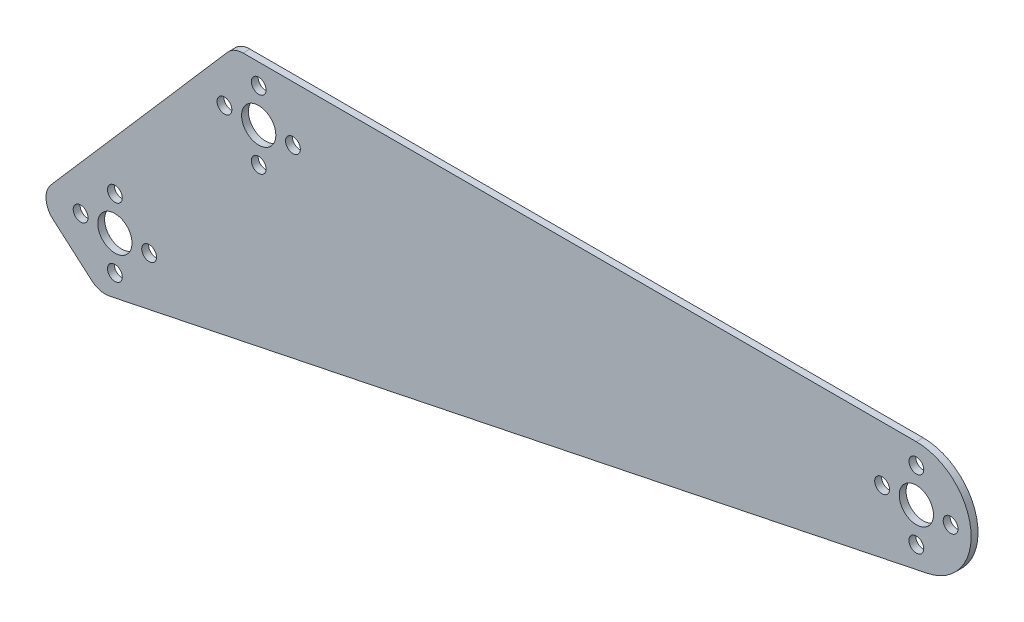
SolidWorks part; units mm, degrees
ref_plane "Front Plane" through (0, 0, 0) normal (0, 0, 1) x (1, 0, 0)
ref_plane "Top Plane" through (0, 0, 0) normal (0, 1, 0) x (1, 0, 0)
ref_plane "Right Plane" through (0, 0, 0) normal (1, 0, 0) x (0, 0, -1)
sketch "Sketch1" plane through (0, 0, 0) normal (0, 0, 1) x (1, 0, 0)
  line L0 (0, 0) -> (-66.6556, -76.6785) construction
  line L1 (55, 0) -> (-55, 0) construction
  line L2 (304.8, 25.4) -> (-7.2347, 25.4)
  line L3 (-96.2402, -71.9956) -> (-14.4233, 22.124)
  line L4 (-69.2153, -103.1424) -> (309.935, -24.8755)
  line L5 (0, 15.875) -> (0, -15.875) construction
  line L6 (-15.875, 0) -> (15.875, 0) construction
  line L7 (-66.6556, -60.8035) -> (-66.6556, -92.5535) construction
  line L8 (-82.5306, -76.6785) -> (-50.7806, -76.6785) construction
  line L9 (-95.3005, -85.4332) -> (-77.3898, -101.0027)
  line L10 (304.8, 0) -> (304.8, 15.875) construction
  circle A0 centre (304.8, 0) radius 7.9375
  circle A1 centre (0, 0) radius 7.9375
  circle A2 centre (-66.6556, -76.6785) radius 7.9375
  arc A7 (304.8, 25.4) -> (309.935, -24.8755) centre (304.8, 0) cw
  arc A8 (-69.2153, -103.1424) -> (-77.3898, -101.0027) centre (-71.1409, -93.8141) cw
  circle A9 centre (0, 15.875) radius 3.429
  circle A10 centre (0, -15.875) radius 3.429
  circle A11 centre (-15.875, 0) radius 3.429
  circle A12 centre (15.875, 0) radius 3.429
  circle A13 centre (-66.6556, -60.8035) radius 3.429
  circle A14 centre (-66.6556, -92.5535) radius 3.429
  circle A15 centre (-82.5306, -76.6785) radius 3.429
  circle A16 centre (-50.7806, -76.6785) radius 3.429
  arc A17 (-95.3005, -85.4332) -> (-96.2402, -71.9956) centre (-89.0515, -78.2446) cw
  arc A18 (-7.2347, 25.4) -> (-14.4233, 22.124) centre (-7.2347, 15.875) ccw
  circle A19 centre (304.8, 0) radius 15.875 construction
  circle A20 centre (304.8, 15.875) radius 3.429
  circle A21 centre (320.675, 0) radius 3.429
  circle A22 centre (304.8, -15.875) radius 3.429
  circle A23 centre (288.925, 0) radius 3.429
  point P21 (0, 0)
  point P26 (0, 0)
  point P32 (-66.6556, -76.6785)
  point P37 (-66.6556, -76.6785)
  point P43 (288.925, 0)
  dimension "D2" = 15.875
  dimension "D5" = 101.6
  dimension "D6" = 25.4
  dimension "D8" = 6.858
  dimension "D15" = 9.525
  dimension "D16" = 31.75
  dimension "D17" = 4
  dimension "D3" = 304.8
  dimension "D4" = 131
  dimension "D7" = 31.75
  dimension "D9" = 31.75
  dimension "D10" = 31.75
  dimension "D11" = 31.75
  dimension "D12" = 25.4
  dimension "D13" = 25.4
  dimension "D14" = 25.4
extrude "Boss-Extrude1" add sketch "Sketch1" along normal blind 3.175
